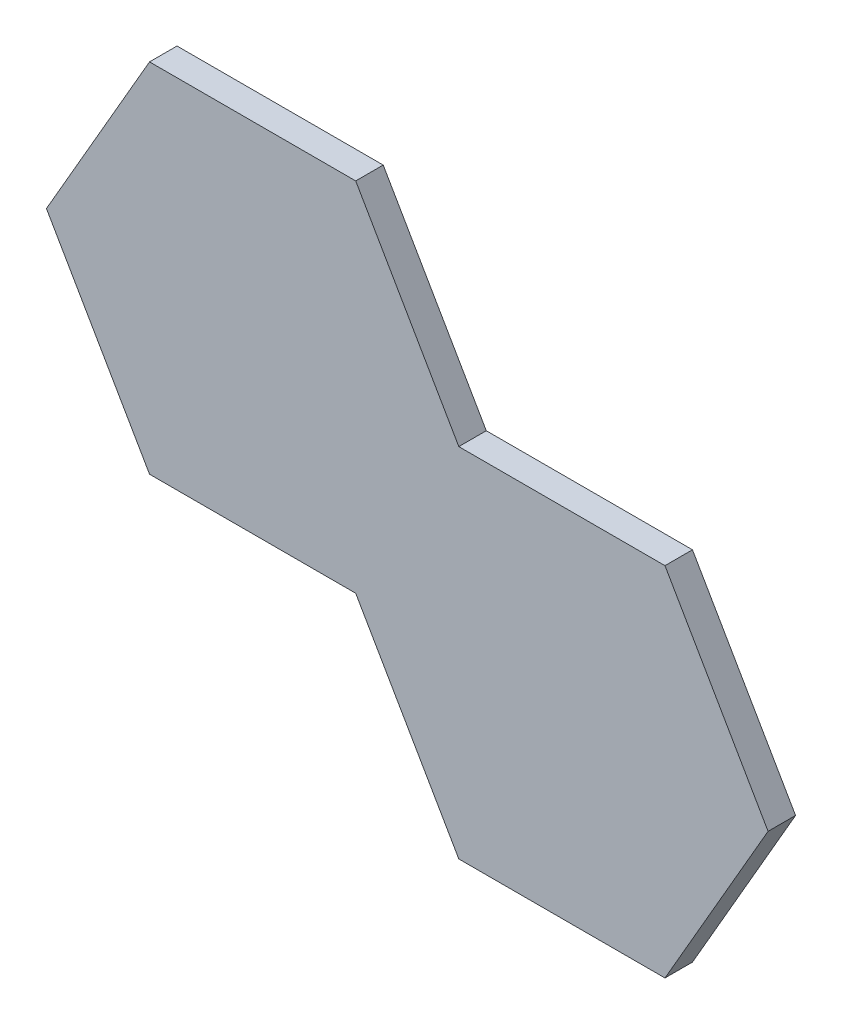
SolidWorks part; units mm, degrees
ref_plane "Front Plane" through (0, 0, 0) normal (0, 0, 1) x (1, 0, 0)
ref_plane "Top Plane" through (0, 0, 0) normal (0, 1, 0) x (1, 0, 0)
ref_plane "Right Plane" through (0, 0, 0) normal (1, 0, 0) x (0, 0, -1)
sketch "Sketch1" plane through (0, 0, 0) normal (0, 0, 1) x (1, 0, 0)
  line L0 (-30, 0) -> (30, 0) construction
  line L1 (-5, -8.6603) -> (5, -8.6603)
  line L2 (5, -8.6603) -> (10, 0)
  line L3 (10, 0) -> (5, 8.6603)
  line L4 (5, 8.6603) -> (-5, 8.6603)
  line L5 (-5, 8.6603) -> (-10, 0)
  line L6 (-10, 0) -> (-5, -8.6603)
  line L7 (-15, -25.9808) -> (15, -25.9808)
  line L8 (15, -25.9808) -> (30, 0)
  line L9 (30, 0) -> (15, 25.9808)
  line L10 (15, 25.9808) -> (-15, 25.9808)
  line L11 (-15, 25.9808) -> (-30, 0)
  line L12 (-30, 0) -> (-15, -25.9808)
  line L13 (0, 25.9808) -> (0, -25.9808) construction
  circle A0 centre (0, 0) radius 8.6603 construction
  circle A1 centre (0, 0) radius 25.9808 construction
  circle A2 centre (-20, 0) radius 5
  circle A3 centre (20, 0) radius 5
  dimension "D3" = 10
  dimension "D1" = 10
  dimension "D2" = 30
  dimension "D4" = 20
extrude "Boss-Extrude1" add sketch "Sketch1" against normal blind 4 contours L11 L12 L7 L8 L9 L10 L6 L5 L4 L3 L2 L1 A2 A3 region at (-21.8126, -12.5935, 0)
extrude "Boss-Extrude2" add sketch "Sketch1<4>" against normal blind 8 contours L5 L6 L1 L2 L3 L4 region at (0, 0, 0)
sketch "Sketch1<4>" plane through (0, 0, 0) normal (0, 0, 1) x (1, 0, 0) same geometry as "Sketch1"
extrude "Boss-Extrude3" add sketch "Sketch1<5>" against normal blind 2 contours A2 | A3 region at (-20, 0, 0) region at (20, 0, 0)
sketch "Sketch1<5>" plane through (0, 0, 0) normal (0, 0, 1) x (1, 0, 0) same geometry as "Sketch1"
mirror "Mirror1" about plane through (22.5, -12.9904, -4) normal (0.866, -0.5, 0) of bodies 103
